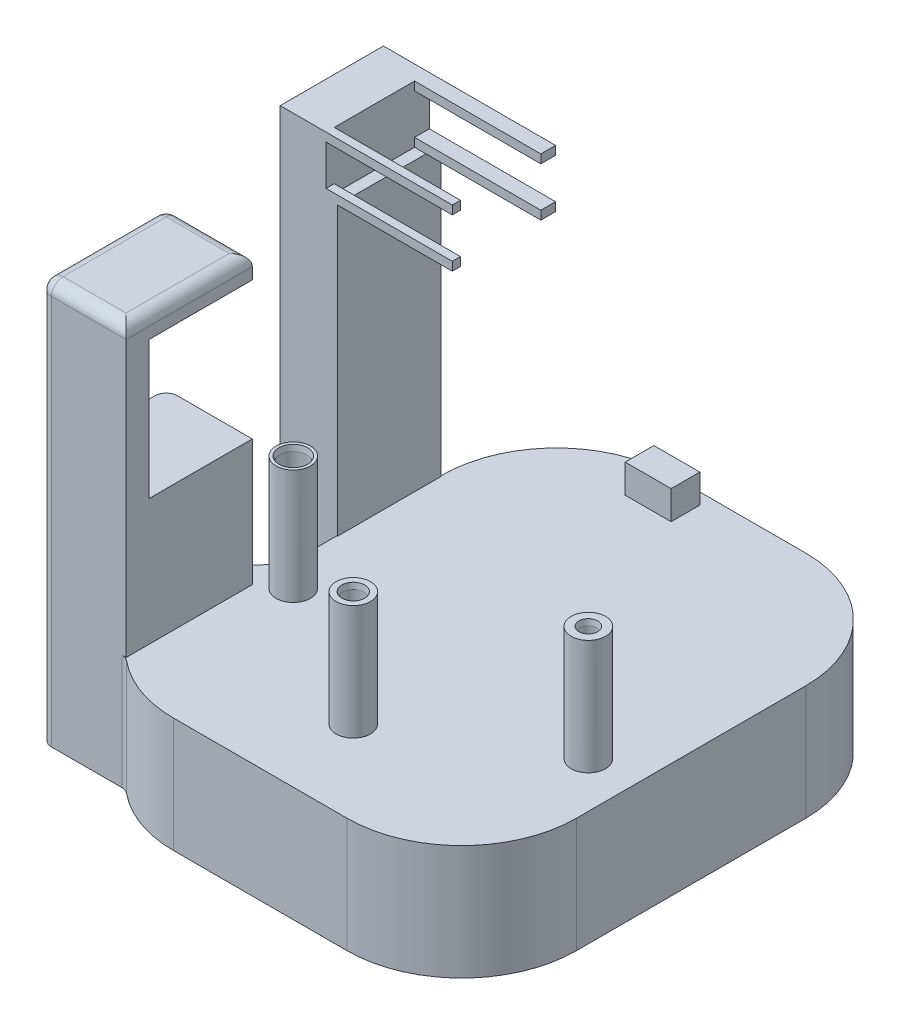
SolidWorks part; units mm, degrees
ref_plane "Front Plane" through (0, 0, 0) normal (0, 0, 1) x (1, 0, 0)
ref_plane "Top Plane" through (0, 0, 0) normal (0, 1, 0) x (1, 0, 0)
ref_plane "Right Plane" through (0, 0, 0) normal (1, 0, 0) x (0, 0, -1)
sketch "Sketch5" plane through (0, 0, 0) normal (0, 1, 0) x (1, 0, 0)
  line L1 (31.75, 40) -> (-31.75, 40)
  line L2 (31.75, 40) -> (31.75, -40)
  line L3 (31.75, -40) -> (-31.75, -40)
  line L4 (-31.75, 40) -> (-31.75, -40)
  line L5 (31.75, 40) -> (-31.75, -40) construction
  line L6 (31.75, -40) -> (-31.75, 40) construction
  point P0 (0, 0)
  dimension "D1" = 80
  dimension "D2" = 63.5
extrude "Boss-Extrude4" add sketch "Sketch5" along normal blind 20
sketch "Sketch6" plane through (0, 20, 0) normal (0, 1, 0) x (1, 0, 0)
  line L0 (31.75, 40) -> (-31.75, 40) construction
  line L1 (-4.75, 38) -> (-12.75, 38)
  line L2 (-4.75, 38) -> (-4.75, 33)
  line L3 (-4.75, 33) -> (-12.75, 33)
  line L4 (-12.75, 38) -> (-12.75, 33)
  line L5 (-4.75, 38) -> (-12.75, 33) construction
  line L6 (-4.75, 33) -> (-12.75, 38) construction
  line L9 (0, 0) -> (0, 40) construction
  line L10 (-31.75, 40) -> (-31.75, -40) construction
  point P0 (-8.75, 35.5)
  dimension "D1" = 8
  dimension "D2" = 5
  dimension "D3" = 2
  dimension "D4" = 19
extrude "Boss-Extrude5" add sketch "Sketch6" along normal blind 5 contours L3 L4 L1 L2
sketch "Sketch9" plane through (0, 0, 0) normal (0, 1, 0) x (1, 0, 0)
  line L0 (-31.75, 40) -> (-31.75, -40) construction
  line L5 (-31.75, -35) -> (-46.75, -35)
  line L6 (-31.75, -35) -> (-31.75, -13)
  line L7 (-31.75, -13) -> (-46.75, -13)
  line L8 (-46.75, -35) -> (-46.75, -13)
  line L9 (-31.75, -40) -> (31.75, -40) construction
  point P13 (-39.25, -13)
  dimension "D4" = 5
  dimension "D5" = 22
  dimension "D6" = 7.5
sketch "Sketch13" plane through (0, 20, 0) normal (0, 1, 0) x (1, 0, 0)
  line L0 (-31.75, 40) -> (-31.75, -40) construction
  line L2 (-31.75, -40) -> (31.75, -40) construction
  circle A0 centre (-27.6098, -10) radius 3
  circle A1 centre (23.8252, -10) radius 3
  circle A2 centre (-1.905, -25.24) radius 3
  dimension "D1" = 4.1402
  dimension "D3" = 6
  dimension "D4" = 51.435
  dimension "D6" = 6
  dimension "D7" = 6
  dimension "D2" = 30
  dimension "D5" = 25.7302
  dimension "D8" = 25.7048
  dimension "D9" = 15.24
extrude "Boss-Extrude8" add sketch "Sketch13" along normal blind 20
extrude "Boss-Extrude10" add sketch "Sketch9" along normal blind 70 contours L8 L7 L6 L5
sketch "Sketch14" plane through (0, 0, 13) normal (0, 0, -1) x (-1, 0, 0)
  line L0 (31.75, 70) -> (31.75, 20) construction
  line L1 (31.75, 42) -> (46.75, 42)
  line L2 (31.75, 42) -> (31.75, 66)
  line L3 (31.75, 66) -> (46.75, 66)
  line L4 (46.75, 42) -> (46.75, 66)
  line L5 (46.75, 70) -> (46.75, 0) construction
  line L7 (31.75, 0) -> (46.75, 0) construction
  dimension "D1" = 42
  dimension "D2" = 24
extrude "Cut-Extrude1" cut sketch "Sketch14" against normal blind 18 contours L3 L4 L1 L2
fillet "Fillet1" radius 20 4 edges at (-31.75, 10, -40) (31.75, 10, -40) (-31.75, 10, 40) (31.75, 10, 40)
fillet "Fillet2" radius 10 1 edges at (-31.75, 10, 13)
fillet "Fillet3" radius 2 3 edges at (-31.75, 10, 35) (-46.75, 35, 35) (-46.75, 21, 13)
fillet "Fillet4" radius 2 1 edges at (-46.75, 68, 13)
fillet "Fillet6" radius 2 6 edges at (-31.75, 70, 24) (-38.25, 70, 35) (-46.1642, 70, 34.4142) (-46.75, 70, 24) (-46.1642, 70, 13.5858) (-38.25, 70, 13)
sketch "Sketch15" plane through (0, 40, 0) normal (0, 1, 0) x (1, 0, 0)
  circle A0 centre (23.8252, -10) radius 1.6383
  circle A1 centre (23.8252, -10) radius 3 construction
  circle A2 centre (-1.905, -25.24) radius 2
  circle A3 centre (-1.905, -25.24) radius 3 construction
  circle A5 centre (-27.6098, -10) radius 2.5
  dimension "D1" = 3.2766
  dimension "D3" = 4
  dimension "D4" = 5
  dimension "D2" = 0
  dimension "D5" = 0
extrude "Cut-Extrude2" cut sketch "Sketch15" against normal blind 1 draft 8
sketch "Sketch16" plane through (0, 39, 0) normal (0, 1, 0) x (1, 0, 0)
  circle A0 centre (23.8252, -10) radius 1.4986
  circle A1 centre (23.8252, -10) radius 3 construction
  circle A2 centre (-1.905, -25.24) radius 2
  circle A3 centre (-27.6098, -10) radius 2.5
  circle A5 centre (-1.905, -25.24) radius 3 construction
  dimension "D1" = 2.9972
  dimension "D3" = 4
  dimension "D4" = 5
  dimension "D2" = 0
  dimension "D6" = 0
extrude "Cut-Extrude3" cut sketch "Sketch16" against normal blind 7
sketch "Sketch18" plane through (0, 0, 0) normal (0, -1, 0) x (-1, 0, 0)
  line L0 (41.75, -13) -> (44.75, -13) construction
  line L1 (31.6319, 19.7413) -> (41.6319, 19.7413)
  line L2 (31.6319, 19.7413) -> (31.6319, 1.7413)
  line L3 (31.6319, 1.7413) -> (41.6319, 1.7413)
  line L4 (41.6319, 19.7413) -> (41.6319, 1.7413)
  point P4 (32.6009, 13.424)
  dimension "D1" = 14.7413
  dimension "D2" = 41.6319
  dimension "D3" = 18
  dimension "D4" = 10
extrude "Boss-Extrude11" add sketch "Sketch18" against normal blind 80 contours L1 L4 L3 L2
sketch "Sketch19" plane through (0, 80, 0) normal (0, 1, 0) x (1, 0, 0)
  line L1 (-31.6319, 19.7413) -> (-11.6319, 19.7413)
  line L2 (-31.6319, 19.7413) -> (-31.6319, 14.7413)
  line L3 (-31.6319, 6.7413) -> (-31.6319, 14.7413)
  line L4 (-11.6319, 19.7413) -> (-11.6319, 14.7413)
  line L5 (-31.6319, 1.7413) -> (-11.6319, 1.7413)
  line L6 (-31.6319, 1.7413) -> (-31.6319, 6.7413)
  line L8 (-11.6319, 1.7413) -> (-11.6319, 6.7413)
  line L9 (-11.6319, 6.7413) -> (-11.6319, 14.7413)
  point P9 (-50.6726, -14.8204)
  dimension "D3" = 20
extrude "Boss-Extrude12" add sketch "Sketch19" against normal blind 10
sketch "Sketch20" plane through (-11.6319, 0, 0) normal (1, 0, 0) x (0, 0, -1)
  line L0 (1.7413, 80) -> (19.7413, 80) construction
  line L1 (17.1678, 80) -> (3.1678, 80)
  line L2 (17.1678, 80) -> (17.1678, 78.5)
  line L3 (17.1678, 70) -> (3.1678, 70)
  line L4 (3.1678, 80) -> (3.1678, 78.5)
  line L5 (1.7413, 70) -> (19.7413, 70) construction
  line L7 (1.7413, 71.5) -> (3.1678, 71.5)
  line L8 (1.7413, 71.5) -> (1.7413, 78.5)
  line L9 (1.7413, 78.5) -> (3.1678, 78.5)
  line L10 (19.7413, 71.5) -> (19.7413, 78.5)
  line L11 (19.7413, 70) -> (19.7413, 80) construction
  line L12 (1.7413, 70) -> (1.7413, 80) construction
  line L13 (3.1678, 71.5) -> (3.1678, 70)
  line L14 (17.1678, 78.5) -> (19.7413, 78.5)
  line L15 (17.1678, 71.5) -> (17.1678, 70)
  line L16 (17.1678, 71.5) -> (19.7413, 71.5)
  point P8 (10.1678, 80)
  point P17 (1.7413, 75)
  dimension "D1" = 7
  dimension "D2" = 3.5
  dimension "D3" = 3.5
  dimension "D4" = 0
extrude "Cut-Extrude4" cut sketch "Sketch20" against normal blind 22 contours L9 L4 L1 L2 L14 L10 L16 L15 L3 L13 L7 L8
